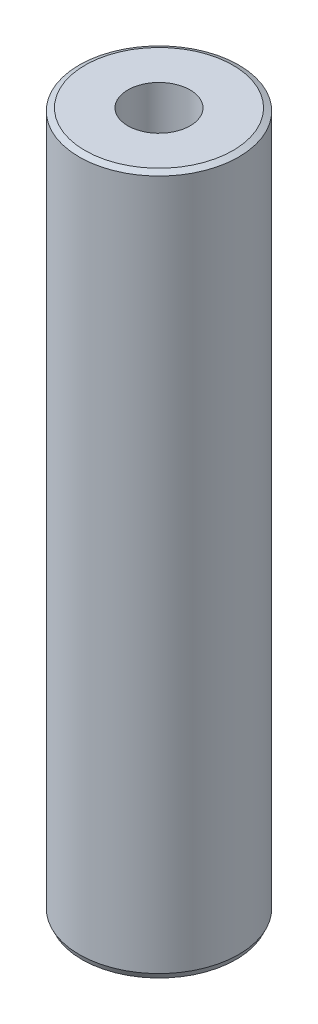
SolidWorks part; units mm, degrees
ref_plane "Front Plane" through (0, 0, 0) normal (0, 0, 1) x (1, 0, 0)
ref_plane "Top Plane" through (0, 0, 0) normal (0, 1, 0) x (1, 0, 0)
ref_plane "Right Plane" through (0, 0, 0) normal (1, 0, 0) x (0, 0, -1)
sketch "Sketch1" plane through (0, 0, 0) normal (0, 1, 0) x (1, 0, 0)
  circle A0 centre (0, 0) radius 10
  dimension "SHAFT_OD" = 20
extrude "Boss-Extrude1" add sketch "Sketch1" along normal blind 87.6767
sketch "Sketch2" plane through (0, 0, 0) normal (0, 1, 0) x (1, 0, 0)
  circle A0 centre (0, 0) radius 3.9067
  dimension "BORE_D" = 7.8135
extrude "Cut-Extrude1" cut sketch "Sketch2" along normal through all
chamfer "Chamfer1" distance 0.3399 angle 64.839 2 edges at (0, 87.6767, 10) (0, 0, 10) first distance on face at (0, 87.6767, 10) first distance on face at (0, 0, 3.9067)
